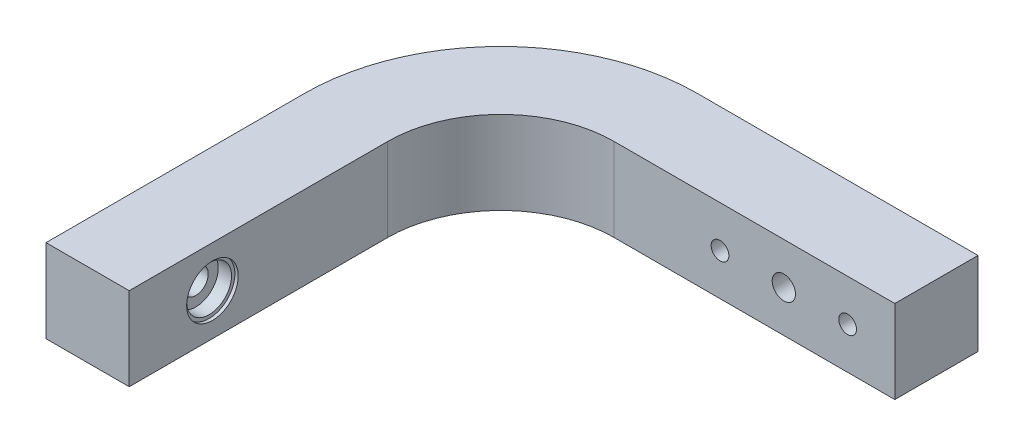
SolidWorks part; units mm, degrees
ref_plane "Front Plane" through (0, 0, 0) normal (0, 0, 1) x (1, 0, 0)
ref_plane "Top Plane" through (0, 0, 0) normal (0, 1, 0) x (1, 0, 0)
ref_plane "Right Plane" through (0, 0, 0) normal (1, 0, 0) x (0, 0, -1)
ref_axis "Z" through (0, 0, -59.2654) along (0, 0, 1)
sketch "Sketch1" plane through (0, 0, 0) normal (0, 1, 0) x (1, 0, 0)
  line L0 (-30.6, 0) -> (30.6, 0) construction
  line L1 (-66, -35.4) -> (-66, -82)
  line L2 (-66, -82) -> (-51, -82)
  line L3 (-51, -82) -> (-51, -35.4)
  line L4 (-30.6, -15) -> (30.6, -15) construction
  line L5 (0, -15) -> (0, 0) construction
  line L6 (51, -82) -> (51, -35.4) construction
  line L7 (66, -82) -> (51, -82) construction
  line L8 (66, -35.4) -> (66, -82) construction
  line L9 (30.6, 0) -> (30.6, -15) construction
  line L10 (20, -15) -> (20, 0)
  line L11 (-30.6, -15) -> (20, -15)
  line L12 (-30.6, 0) -> (20, 0)
  line L13 (0, 59.2654) -> (0, -30.9346) construction
  arc A0 (-30.6, 0) -> (-66, -35.4) centre (-30.6, -35.4) ccw
  arc A1 (-51, -35.4) -> (-30.6, -15) centre (-30.6, -35.4) cw
  arc A2 (51, -35.4) -> (30.6, -15) centre (30.6, -35.4) ccw construction
  arc A3 (30.6, 0) -> (66, -35.4) centre (30.6, -35.4) cw construction
  dimension "D3" = 20.4
  dimension "D1" = 102
  dimension "D2" = 15
  dimension "D4" = 67
  dimension "D5" = 20
extrude "Boss-Extrude1" add sketch "Sketch1" along normal blind 7.5 and the other way blind 7.5
sketch "Sketch2" plane through (-51, 0, 0) normal (-1, 0, 0) x (0, 0, 1)
  line L1 (45.1, 0) -> (-45.1, 0) construction
  line L2 (0, -8.25) -> (0, 8.25) construction
  circle A0 centre (67, 0) radius 2.25
  dimension "D1" = 4.5
  dimension "D2" = 67
extrude "Cut-Extrude1" cut sketch "Sketch2" against normal through all both and the other way through all
ref_axis "Axis2" through (-85.609, 0, 67) along (1, 0, 0)
sketch "Sketch3" plane through (0, 0, 0) normal (0, 0, -1) x (-1, 0, 0)
  line L0 (-11.5, 0) -> (11.5, 0) construction
  circle A0 centre (0, 0) radius 2.1
  circle A1 centre (-11.5, 0) radius 1.6
  circle A2 centre (11.5, 0) radius 1.6
  dimension "D1" = 4.2
  dimension "D3" = 3.2
  dimension "D2" = 23
extrude "Cut-Extrude2" cut sketch "Sketch3" against normal through all
sketch "Sketch5" plane through (0, 0, 0) normal (0, 1, 0) x (1, 0, 0)
  line L0 (-66, -71.65) -> (-65.4, -71.65)
  line L1 (-65.4, -71.65) -> (-65.4, -71.05)
  line L2 (-65.4, -71.05) -> (-63, -71.05)
  line L3 (-63, -71.05) -> (-63, -67)
  line L4 (-66, -71.65) -> (-66, -67)
  line L5 (-85.609, -67) -> (-36.8905, -67) construction
  line L6 (-84.5878, -67) -> (-79.7197, -67) construction
  line L7 (-66, -67) -> (-63, -67)
  line L9 (-66, -35.4) -> (-66, -82) construction
  line L10 (-58.5, -78.0435) -> (-58.5, -69.815) construction
  line L11 (-66, -82) -> (-51, -82) construction
  line L12 (-51, -67) -> (-54, -67)
  line L13 (-51, -71.65) -> (-51, -67)
  line L14 (-54, -71.05) -> (-54, -67)
  line L15 (-51.6, -71.05) -> (-54, -71.05)
  line L16 (-51.6, -71.65) -> (-51.6, -71.05)
  line L17 (-51, -71.65) -> (-51.6, -71.65)
  point P14 (-58.5, -82)
  dimension "D1" = 0.6
  dimension "D2" = 4.65
  dimension "D3" = 8.1
  dimension "D4" = 3
revolve "bearing-seats" cut sketch "Sketch5" angle 360 about L6
equation "\"width\"= \"EyeDiameter\" + \"EyeClearance\""
equation "\"prongwidth\"= \"L2Thickness\""
equation "\"D2@Sketch1\"=\"prongwidth\""
equation "\"D3@Sketch1\"=\"width\"/5"
equation "\"pronglength\"= \"BasePlaneDistance\"'model implicitly adds clearance (of prongwidth) to the hole drilled at the baseplanedistance"
equation "\"D4@Sketch1\"=\"pronglength\""
equation "\"D1@Boss-Extrude1\"=\"prongwidth\"/2"
equation "\"D2@Boss-Extrude1\"=\"prongwidth\"/2"
equation "\"lbracket-plane-to-axis\"= \"BasePlaneDistance\""
equation "\"D2@Sketch2\"=\"lbracket-plane-to-axis\""
equation "\"EyeDiameter\" = 100"
equation "\"BasePlaneDistance\" = \"EyeDiameter\"/2+\"L2Thickness\"+\"EyeClearance\""
equation "\"EyeClearance\" = 2"
equation "\"D1@Sketch1\"=\"EyeDiameter\"+\"EyeClearance\""
equation "\"BearingDepth\"= 6"
equation "\"BearingHousingID\"=4.5"
equation "\"BearingFlangeThickness\"= 0.75"
equation "\"BearingFlangeOD\"=7.5"
equation "\"PrinterFilamentThickness\"= 0.1"
equation "\"ApplyPrinterOffset\"= 1'if 1, adjust hole sizes to try and make pressfits work with the 3d printer"
equation "\"L2Thickness\" = 3.75 * \"shaft_diameter\""
equation "\"L2_ID\" = 20"
equation "\"vx\" = 0"
equation "\"vy\" = 0"
equation "\"vz\" = 100"
equation "\"parametric_end\" = 1"
equation "\"Rw_3_xx\" = -(\"vz\")/sqr((\"vx\")^2 + (\"vz\")^2)"
equation "\"Rw_3_xy\" = 0"
equation "\"Rw_3_xz\" = (\"vx\")/sqr((\"vx\")^2 + (\"vz\")^2)"
equation "\"Rw_3_zx\" = (\"vx\")/sqr((\"vx\")^2 + (\"vy\")^2 + (\"vz\")^2)"
equation "\"Rw_3_zy\" = (\"vy\")/sqr((\"vx\")^2 + (\"vy\")^2 + (\"vz\")^2)"
equation "\"Rw_3_zz\" = (\"vz\")/sqr((\"vx\")^2 + (\"vy\")^2 + (\"vz\")^2)"
equation "\"Rw_3_yx\" = (\"vx\")*(\"vy\")/sqr((\"vx\")^4 + (\"vx\")^2*(\"vy\")^2 + 2*(\"vx\")^2*(\"vz\")^2 + (\"vy\")^2*(\"vz\")^2 + (\"vz\")^4)"
equation "\"Rw_3_yy\" = -sqr((\"vx\")^2 + (\"vz\")^2)/sqr((\"vx\")^2 + (\"vy\")^2 + (\"vz\")^2)"
equation "\"Rw_3_yz\" = (\"vy\")*(\"vz\")/sqr((\"vx\")^4 + (\"vx\")^2*(\"vy\")^2 + 2*(\"vx\")^2*(\"vz\")^2 + (\"vy\")^2*(\"vz\")^2 + (\"vz\")^4)"
equation "\"O2Targx\" = -\"BasePlaneDistance\"*(\"vx\")*(\"vy\")/sqr((\"vx\")^4 + (\"vx\")^2*(\"vy\")^2 + 2*(\"vx\")^2*(\"vz\")^2 + (\"vy\")^2*(\"vz\")^2 + (\"vz\")^4)"
equation "\"O2Targy\" = \"BasePlaneDistance\"*sqr((\"vx\")^2 + (\"vz\")^2)/sqr((\"vx\")^2 + (\"vy\")^2 + (\"vz\")^2)"
equation "\"O2Targz\" = -\"BasePlaneDistance\"*(\"vy\")*(\"vz\")/sqr((\"vx\")^4 + (\"vx\")^2*(\"vy\")^2 + 2*(\"vx\")^2*(\"vz\")^2 + (\"vy\")^2*(\"vz\")^2 + (\"vz\")^4)"
equation "\"O2Targx_0\" = -(\"BasePlaneDistance\")*sqr((\"vx\")^2 + (\"vz\")^2)/sqr((\"vx\")^2 + (\"vy\")^2 + (\"vz\")^2)"
equation "\"O2Targy_0\" = -(\"BasePlaneDistance\")*(\"vy\")*(\"vz\")/sqr((\"vx\")^4 + (\"vx\")^2*(\"vy\")^2 + 2*(\"vx\")^2*(\"vz\")^2 + (\"vy\")^2*(\"vz\")^2 + (\"vz\")^4)"
equation "\"O2Targz_0\" = (\"BasePlaneDistance\")*(\"vx\")*(\"vy\")/sqr((\"vx\")^4 + (\"vx\")^2*(\"vy\")^2 + 2*(\"vx\")^2*(\"vz\")^2 + (\"vy\")^2*(\"vz\")^2 + (\"vz\")^4) + (\"BasePlaneDistance\")"
equation "\"theta2_s1\" = arcsin(((\"BasePlaneDistance\") - (\"O2Targz_0\"))/(\"BasePlaneDistance\")) + pi"
equation "\"theta2_s2\" = -arcsin(((\"BasePlaneDistance\") - (\"O2Targz_0\"))/(\"BasePlaneDistance\"))"
equation "\"theta1_s1\" = arcsin((\"O2Targy_0\")/((\"BasePlaneDistance\")*cos((\"Theta2\")))) + pi"
equation "\"theta1_s2\" = -arcsin((\"O2Targy_0\")/((\"BasePlaneDistance\")*cos((\"Theta2\"))))"
equation "\"theta1_s3\" = -arccos(-(\"O2Targx_0\")/((\"BasePlaneDistance\")*cos((\"Theta2\")))) + 2*pi"
equation "\"theta1_s4\" = arccos(-(\"O2Targx_0\")/((\"BasePlaneDistance\")*cos((\"Theta2\"))))"
equation "\"Theta1\" = \"theta1_s2\" 'so far, theta1_s1 and theta1_s4 have agreed, and they agree with the sw constraint solver"
equation "\"Theta2\" = \"theta2_s2\""
equation "\"o2_x\" = -(\"BasePlaneDistance\")*cos((\"Theta1\"))*cos((\"Theta2\"))"
equation "\"o2_y\" = -(\"BasePlaneDistance\")*sin((\"Theta1\"))*cos((\"Theta2\"))"
equation "\"o2_z\" = (\"BasePlaneDistance\")*(sin((\"Theta2\")) + 1)"
equation "\"o1_x\" = (\"BasePlaneDistance\")*sin((\"Theta1\"))"
equation "\"o1_y\" = -(\"BasePlaneDistance\")*cos((\"Theta1\"))"
equation "\"o1_z\" = (\"BasePlaneDistance\")"
equation "\"Actuator1_Theta\" = atn(\"vx\"/\"vz\") 'ik solution for the single link joint"
equation "\"Actuator2_Theta\" = \"Theta1\"  'ik solution for the double link joint"
equation "\"MotorBaseThickness\" = 3 "
equation "\"BaseThickness\" = 3 "
equation "\"EncoderToMagnetAirgap\" = 1 'Encoder to magnet airgap"
equation "\"EncoderHeight\" = 1.192  'Height of the encoder"
equation "\"MagnetThickness\" = 0.5  'Magnet thickness"
equation "\"pcb_thickness\" = 1.6  'Thickness of the PCB"
equation "\"pcb_outer_diameter\" = 32 'the OD of the pcb"
equation "\"shaft_diameter\" = 4"
equation "\"D1@Sketch2\"=\"shaft_diameter\"*1.125"
equation "\"D2@Sketch5\"=\"ApplyPrinterOffset\" * \"PrinterFilamentThickness\" / 2 + 4.6"
equation "\"D3@Sketch5\"= \"ApplyPrinterOffset\" * \"PrinterFilamentThickness\"  + 8.00"
